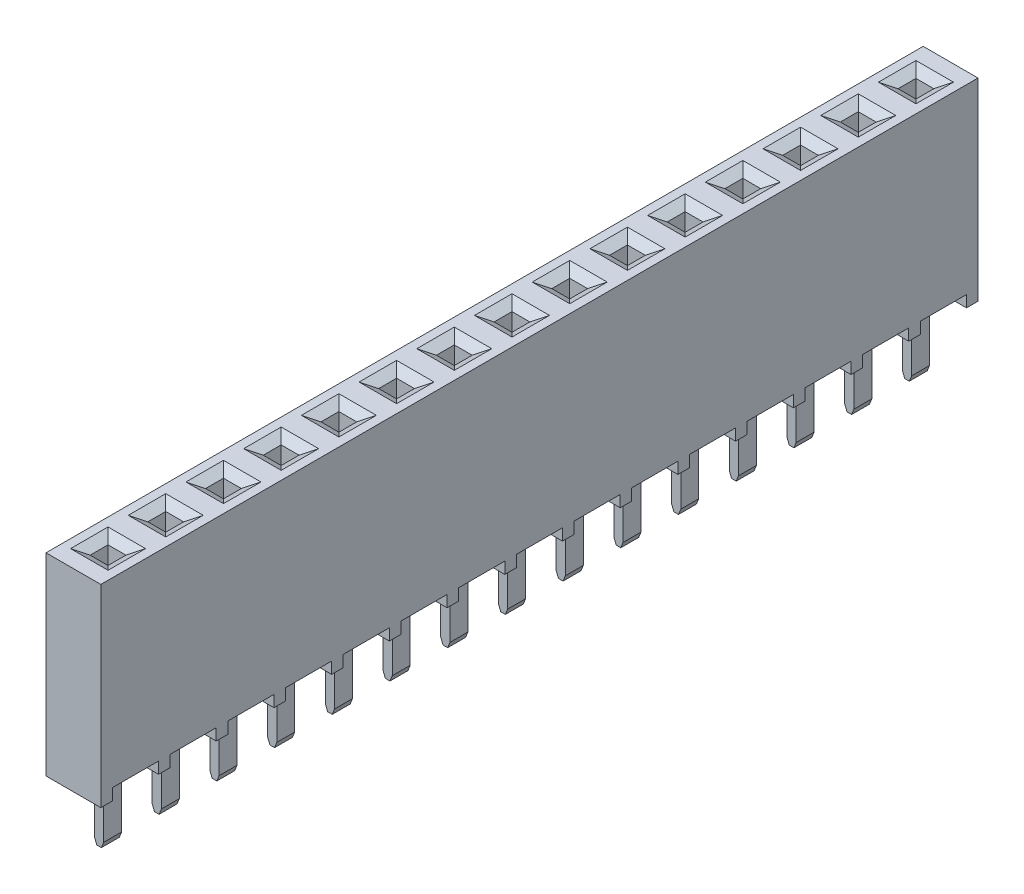
SolidWorks part; units mm, degrees
ref_plane "Front" through (0, 0, 0) normal (0, 0, 1) x (1, 0, 0)
ref_plane "Top" through (0, 0, 0) normal (0, 1, 0) x (1, 0, 0)
ref_plane "Right" through (0, 0, 0) normal (1, 0, 0) x (0, 0, -1)
sketch "Sketch1" plane through (0, 0, 0) normal (0, 1, 0) x (1, 0, 0)
  line L0 (-1.2065, -19.304) -> (1.2065, 19.304) construction
  line L1 (-1.2065, 19.304) -> (1.2065, 19.304)
  line L2 (-1.2065, 19.304) -> (-1.2065, -19.304)
  line L3 (-1.2065, -19.304) -> (1.2065, -19.304)
  line L4 (1.2065, 19.304) -> (1.2065, -19.304)
  dimension "D1" = 38.608
  dimension "D2" = 2.413
extrude "Main Body" add sketch "Sketch1" along normal blind 8.509
ref_plane "Plane1" through (0, 0, -15.24) normal (0, 0, -1) x (-1, 0, 0)
ref_plane "Plane2" through (0, 0, -17.78) normal (0, 0, -1) x (-1, 0, 0)
ref_plane "Plane3" through (0, 0, 0) normal (0, 0, 1) x (1, 0, 0)
ref_plane "Plane4" through (0, 0, -2.54) normal (0, 0, 1) x (1, 0, 0)
sketch "Sketch5" plane through (1.2065, 0, 0) normal (1, 0, 0) x (0, 0, -1)
  line L0 (-19.304, 0) -> (19.304, 0) construction
  line L1 (16.764, 0) -> (18.796, 0)
  line L2 (16.764, 0) -> (16.764, 0.508)
  line L3 (16.764, 0.508) -> (18.796, 0.508)
  line L4 (18.796, 0) -> (18.796, 0.508)
  line L5 (17.78, 0.7418) -> (17.78, -0.7099) construction
  line L6 (19.304, 8.509) -> (19.304, 0) construction
  dimension "D1" = 0.508
  dimension "D2" = 1.524
  dimension "D3" = 0.508
extrude "Cut-Extrude2" cut sketch "Sketch5" against normal up to next
pattern_linear "LPattern1" count 15 spacing 2.54 along (0, 0, 1) of "Cut-Extrude2"
sketch "Sketch2" plane through (0, 8.509, 0) normal (0, 1, 0) x (-1, 0, 0)
  line L0 (0, -0.6833) -> (0, -4.4888) construction
  line L1 (-0.3937, -18.1737) -> (0.3937, -18.1737)
  line L2 (-0.3937, -18.1737) -> (-0.3937, -17.3863)
  line L3 (-0.3937, -17.3863) -> (0.3937, -17.3863)
  line L4 (0.3937, -18.1737) -> (0.3937, -17.3863)
  line L5 (0, 0) -> (-2.54, 0) construction
  line L6 (0.3937, -18.1737) -> (-0.3937, -17.3863) construction
  line L8 (-1.2065, -19.304) -> (1.2065, -19.304) construction
  line L9 (-1.2065, 19.304) -> (-1.2065, -19.304) construction
  point P8 (0, -17.78)
  dimension "D1" = 1.524
  dimension "D2" = 0.7874
  dimension "D3" = 0.7874
  dimension "D4" = 1.2065
extrude "Cut-Extrude1" cut sketch "Sketch2" against normal through all
chamfer "Chamfer1" distance 0.4318 angle 30 4 edges at (0, 8.509, -18.1737) (-0.3937, 8.509, -17.78) (0, 8.509, -17.3863) (0.3937, 8.509, -17.78) first distance on face at (0, 8.509, -17.78)
pattern_linear "LPattern2" count 15 spacing 2.54 along (0, 0, 1) of "Chamfer1", "Cut-Extrude1"
sketch "Sketch4" plane through (0, 0, -17.78) normal (0, 0, -1) x (-1, 0, 0)
  line L0 (0, 2.0688) -> (0, -17.6627) construction
  line L1 (0.3937, 0.508) -> (0.3937, 8.2597) construction
  line L2 (-0.3937, 0.508) -> (-0.3937, 8.2597) construction
  line L3 (-0.3937, 1.016) -> (0.3937, 1.016)
  line L5 (-0.2032, 0.889) -> (-0.2032, -2.3876)
  line L6 (-0.1016, -2.6416) -> (0.1016, -2.6416)
  line L7 (0.2032, 0.889) -> (0.2032, -2.3876)
  line L8 (0.1016, -2.6416) -> (0.2032, -2.3876)
  line L9 (-0.2032, -2.3876) -> (-0.1016, -2.6416)
  line L10 (-1.2065, 0) -> (1.2065, 0) construction
  line L11 (0.3937, 1.016) -> (0.3937, 0.889)
  line L12 (0.3937, 0.889) -> (0.2032, 0.889)
  line L13 (-0.2032, 0.889) -> (-0.3937, 0.889)
  line L14 (-0.3937, 0.889) -> (-0.3937, 1.016)
  dimension "D1" = 0.254
  dimension "D2" = 0.2032
  dimension "D3" = 0.4064
  dimension "D4" = 2.6416
  dimension "D5" = 0.7874
  dimension "D6" = 0.889
  dimension "D7" = 1.016
extrude "PIN" add sketch "Sketch4" along normal mid plane 0.7874
pattern_linear "LPattern4" count 15 spacing 2.54 along (0, 0, 1) of "PIN"
sketch "Sketch7" plane through (0, 0, -17.78) normal (0, 0, -1) x (-1, 0, 0)
  line L0 (-0.2032, 1.016) -> (-0.2032, -0.9144)
  line L1 (0.6096, -1.3208) -> (1.4605, -1.3208)
  line L2 (1.4605, -1.3208) -> (1.4605, -1.7272)
  line L3 (1.4605, -1.7272) -> (0.6096, -1.7272)
  line L4 (0.2032, -0.9144) -> (0.2032, 1.016)
  line L5 (-0.2032, 1.016) -> (-0.3937, 1.016)
  line L6 (0, 1.4788) -> (0, -2.2478) construction
  line L10 (1.2065, 8.509) -> (1.2065, 0) construction
  line L11 (-0.3937, 1.016) -> (-0.3937, 1.27)
  line L12 (-0.3937, 1.27) -> (0.3937, 1.27)
  line L13 (0.3937, 1.27) -> (0.3937, 1.016)
  line L14 (0.3937, 1.016) -> (0.2032, 1.016)
  line L16 (1.4605, -1.524) -> (-2.3476, -1.524) construction
  line L17 (-1.2065, 0) -> (1.2065, 0) construction
  line L18 (1.2065, 0.508) -> (-1.2065, 0.508) construction
  arc A0 (-0.2032, -0.9144) -> (0.6096, -1.7272) centre (0.6096, -0.9144) ccw
  arc A1 (0.6096, -1.3208) -> (0.2032, -0.9144) centre (0.6096, -0.9144) cw
  dimension "D9" = 0.8128
  dimension "D10" = 0.4064
  dimension "D1" = 1.2065
  dimension "D2" = 0.4064
  dimension "D3" = 0.4064
  dimension "D4" = 1.524
  dimension "D6" = 0.7874
  dimension "D7" = 0.762
  dimension "D8" = 0.254
  dimension "A" = 0.254
sketch "Sketch8" plane through (0, 0, -15.24) normal (0, 0, -1) x (-1, 0, 0)
  line L0 (0.2032, 1.016) -> (0.2032, -0.9144)
  line L1 (-0.3937, 1.27) -> (0.3937, 1.27)
  line L2 (1.2065, 8.509) -> (1.2065, 0) construction
  line L3 (0.3937, 1.016) -> (0.2032, 1.016)
  line L5 (-0.3937, 1.016) -> (-0.3937, 1.27)
  line L6 (0.3937, 1.016) -> (0.3937, 1.27)
  line L7 (-1.2065, 0) -> (1.2065, 0) construction
  line L8 (-0.2032, 1.016) -> (-0.2032, -0.9144)
  line L9 (0, 1.9479) -> (0, -2.4889) construction
  line L10 (2.9301, -1.524) -> (0.4606, -1.524) construction
  line L11 (1.2065, 8.509) -> (1.2065, 0) construction
  line L13 (-0.2032, 1.016) -> (-0.2032, -3.4544)
  line L15 (0.6096, -1.7272) -> (1.4605, -1.7272)
  line L16 (1.4605, -1.7272) -> (1.4605, -1.3208)
  line L17 (1.4605, -1.3208) -> (0.6096, -1.3208)
  line L18 (0.6096, -4.2672) -> (1.4605, -4.2672)
  line L19 (0.2032, -3.4544) -> (0.2032, 1.016)
  line L20 (1.4605, -3.8608) -> (0.6096, -3.8608)
  line L21 (1.4605, -4.2672) -> (1.4605, -3.8608)
  line L22 (0.3937, 1.27) -> (-0.3937, 1.27)
  line L23 (-0.3937, 1.016) -> (-0.2032, 1.016)
  line L24 (0.2032, 1.016) -> (0.3937, 1.016)
  line L25 (0.3937, 1.016) -> (0.3937, 1.27)
  line L26 (-0.3937, 1.016) -> (-0.3937, 1.27)
  line L27 (0.3937, 0.508) -> (0.3937, 0.889) construction
  line L28 (-0.3937, 0.508) -> (-0.3937, 0.889) construction
  line L29 (0, 1.27) -> (0, -2.4889) construction
  line L30 (1.4605, -4.064) -> (1.27, -4.064) construction
  line L31 (-0.2032, 1.016) -> (-0.3937, 1.016)
  arc A0 (0.6096, -3.8608) -> (0.2032, -3.4544) centre (0.6096, -3.4544) cw
  arc A1 (0.6096, -4.2672) -> (-0.2032, -3.4544) centre (0.6096, -3.4544) cw
  arc A2 (0.6096, -1.7272) -> (-0.2032, -0.9144) centre (0.6096, -0.9144) cw
  arc A3 (0.6096, -1.3208) -> (0.2032, -0.9144) centre (0.6096, -0.9144) cw
  dimension "D5" = 0.8128
  dimension "D6" = 0.4064
  dimension "D14" = 0.4064
  dimension "D15" = 0.8128
  dimension "D1" = 1.27
  dimension "D2" = 0.254
  dimension "D3" = 0.4064
  dimension "D4" = 0.4064
  dimension "D7" = 1.524
  dimension "D8" = 0.4064
  dimension "D9" = 0.254
  dimension "D10" = 2.54
  dimension "D11" = 0.4064
  dimension "D12" = 1.2065
sketch "Sketch9" plane through (0, 0, -15.24) normal (0, 0, -1) x (-1, 0, 0)
  line L0 (0, 1.6049) -> (0, -3.2713) construction
  line L1 (-2.9337, 1.016) -> (-2.9337, 1.27)
  line L2 (0.3937, 1.27) -> (-0.3937, 1.27)
  line L4 (-2.1463, 1.27) -> (-2.9337, 1.27)
  line L5 (0.3937, 1.016) -> (0.3937, 1.27)
  line L6 (-2.3368, 1.016) -> (-2.1463, 1.016)
  line L7 (-0.3937, 1.016) -> (-0.3937, 1.27)
  line L8 (-0.3937, 1.016) -> (-0.2032, 1.016)
  line L10 (0.3937, 1.27) -> (-0.3937, 1.27)
  line L11 (-2.1463, 1.27) -> (-2.1463, 1.016)
  line L12 (-1.9304, -4.2672) -> (1.4605, -4.2672)
  line L13 (1.4605, -4.2672) -> (1.4605, -3.8608)
  line L14 (1.4605, -3.8608) -> (-1.9304, -3.8608)
  line L15 (0.2032, -5.9944) -> (0.2032, 1.016)
  line L16 (-0.3937, 1.016) -> (-0.3937, 1.27)
  line L17 (-0.2032, 1.016) -> (-0.2032, -5.9944)
  line L18 (-0.3937, 1.016) -> (-0.2032, 1.016)
  line L19 (0.2032, 1.016) -> (0.3937, 1.016)
  line L20 (0.3937, 1.27) -> (0.3937, 1.016)
  line L21 (0.2032, -0.9144) -> (0.2032, 1.016)
  line L22 (-0.2032, 1.016) -> (-0.2032, -0.9144)
  line L24 (1.2065, 8.509) -> (1.2065, 0) construction
  line L25 (1.4605, -1.7272) -> (1.4605, -1.3208)
  line L26 (1.4605, -1.3208) -> (0.6096, -1.3208)
  line L27 (-2.3368, -3.4544) -> (-2.3368, 1.016)
  line L29 (-2.7432, 1.016) -> (-2.7432, -3.4544)
  line L31 (-1.2065, 0) -> (1.2065, 0) construction
  line L32 (0.6096, -1.7272) -> (1.4605, -1.7272)
  line L34 (6.2865, -1.524) -> (4.283, -1.524) construction
  line L35 (6.2865, -4.064) -> (4.7316, -4.064) construction
  line L40 (-2.7432, 1.016) -> (-2.9337, 1.016)
  line L41 (-2.54, 1.27) -> (-2.54, -1.7272) construction
  line L42 (0.2032, 1.016) -> (0.3937, 1.016)
  line L43 (0.3937, 0.508) -> (0.3937, 0.889) construction
  line L44 (-0.3937, 0.508) -> (-0.3937, 0.889) construction
  line L45 (0, 1.27) -> (0, -1.198) construction
  line L46 (0.6096, -6.4008) -> (1.4605, -6.4008)
  line L47 (1.4605, -6.4008) -> (1.4605, -6.8072)
  line L48 (1.4605, -6.8072) -> (0.6096, -6.8072)
  line L49 (6.1112, -6.604) -> (4.5563, -6.604) construction
  arc A0 (0.2032, -0.9144) -> (0.6096, -1.3208) centre (0.6096, -0.9144) ccw
  arc A1 (-0.2032, -0.9144) -> (0.6096, -1.7272) centre (0.6096, -0.9144) ccw
  arc A2 (-1.9304, -4.2672) -> (-2.7432, -3.4544) centre (-1.9304, -3.4544) cw
  arc A3 (-1.9304, -3.8608) -> (-2.3368, -3.4544) centre (-1.9304, -3.4544) cw
  arc A4 (0.6096, -6.4008) -> (0.2032, -5.9944) centre (0.6096, -5.9944) cw
  arc A5 (0.6096, -6.8072) -> (-0.2032, -5.9944) centre (0.6096, -5.9944) cw
  dimension "D7" = 1.27
  dimension "D8" = 0.254
  dimension "D11" = 0.4064
  dimension "D12" = 0.8128
  dimension "D4" = 0.4064
  dimension "D5" = 0.8128
  dimension "D15" = 0.4064
  dimension "D16" = 0.8128
  dimension "D2" = 1.524
  dimension "D3" = 0.4064
  dimension "D6" = 0.4064
  dimension "D9" = 1.2065
  dimension "D10" = 2.54
  dimension "D13" = 0.4064
  dimension "D14" = 5.08
  dimension "D17" = 0.4064
  dimension "D18" = 2.54
  dimension "D19" = 0.7874
  dimension "D20" = 0.7874
  dimension "A" = 0.254
sketch "Sketch10" plane through (0, 0, -15.24) normal (0, 0, -1) x (-1, 0, 0)
  line L0 (-2.54, -14.478) -> (-2.54, 0.635)
  line L2 (-0.508, -16.51) -> (-0.2286, -16.51)
  line L3 (-1.2065, 0) -> (1.2065, 0) construction
  line L4 (1.2065, 8.509) -> (1.2065, 0) construction
  arc A0 (-2.54, -14.478) -> (-0.508, -16.51) centre (-0.508, -14.478) ccw
  dimension "D1" = 2.032
  dimension "D5" = 0.635
  dimension "D2" = 16.51
  dimension "D3" = 0.2794
  dimension "D4" = 3.7465
sketch "Sketch6" plane through (0, 0.508, 0) normal (0, 1, 0) x (-1, 0, 0)
  line L0 (-1.2065, -19.304) -> (1.2065, -19.304) construction
  line L3 (-1.7145, -18.6055) -> (-3.3655, -18.6055)
  line L6 (-3.3655, -18.6055) -> (-3.3655, -16.9545)
  line L8 (-3.3655, -16.9545) -> (-1.7145, -16.9545)
  line L10 (-1.7145, -16.9545) -> (-1.7145, -18.6055)
  line L11 (-3.3655, -17.78) -> (-1.7145, -17.78) construction
  line L12 (-2.54, -18.6055) -> (-2.54, -16.9545) construction
  line L14 (1.2065, -19.304) -> (1.2065, 19.304) construction
  dimension "D1" = 1.651
  dimension "D2" = 3.7465
  dimension "D3" = 1.524
sketch "Sketch11" plane through (0, 0, -15.24) normal (0, 0, -1) x (-1, 0, 0)
  line L0 (-0.2032, 1.016) -> (-0.2032, -0.4572)
  line L1 (-2.5781, -1.27) -> (-0.6096, -1.27)
  line L2 (-0.6096, -0.8636) -> (-2.5781, -0.8636)
  line L3 (-2.5781, -0.8636) -> (-2.5781, -1.27)
  line L4 (0.2032, -0.4572) -> (0.2032, 1.016)
  line L5 (0.3937, 1.27) -> (0.3937, 1.016)
  line L6 (0.3937, 1.016) -> (0.2032, 1.016)
  line L7 (0.3937, 1.27) -> (-0.3937, 1.27)
  line L8 (-0.3937, 1.27) -> (-0.3937, 1.016)
  line L9 (-0.3937, 1.016) -> (-0.2032, 1.016)
  line L10 (-0.3937, 0.508) -> (-0.3937, 0.889) construction
  line L11 (-1.2065, 8.509) -> (-1.2065, 0) construction
  line L12 (0, 1.27) -> (0, -1.1346) construction
  line L13 (-1.2065, 0) -> (1.2065, 0) construction
  arc A0 (-0.2032, -0.4572) -> (-0.6096, -0.8636) centre (-0.6096, -0.4572) cw
  arc A1 (-0.6096, -1.27) -> (0.2032, -0.4572) centre (-0.6096, -0.4572) ccw
  dimension "D7" = 1.27
  dimension "D4" = 0.4064
  dimension "D5" = 0.8128
  dimension "D1" = 0.4064
  dimension "D2" = 1.2065
  dimension "D3" = 1.27
  dimension "D6" = 0.4064
  dimension "L" = 2.5781
sketch "Sketch12" plane through (0, 0, -17.78) normal (0, 0, -1) x (-1, 0, 0)
  line L1 (0.3937, 1.27) -> (-0.3937, 1.27)
  line L3 (-0.3937, 1.016) -> (-0.2032, 1.016)
  line L5 (0.3937, 1.016) -> (0.3937, 1.27)
  line L6 (0, 1.27) -> (0, -2.7927) construction
  line L7 (2.5781, -0.8636) -> (2.5781, -1.27)
  line L8 (2.5781, -1.27) -> (0.6096, -1.27)
  line L9 (0.6096, -0.8636) -> (2.5781, -0.8636)
  line L10 (0.2032, 1.016) -> (0.3937, 1.016)
  line L11 (1.2065, 8.509) -> (1.2065, 0) construction
  line L12 (0.2032, -0.4572) -> (0.2032, 1.016)
  line L13 (-1.2065, 0) -> (1.2065, 0) construction
  line L14 (-0.2032, 1.016) -> (-0.2032, -0.4572)
  line L19 (-0.3937, 1.016) -> (-0.3937, 1.27)
  arc A0 (0.6096, -0.8636) -> (0.2032, -0.4572) centre (0.6096, -0.4572) cw
  arc A1 (0.6096, -1.27) -> (-0.2032, -0.4572) centre (0.6096, -0.4572) cw
  dimension "D7" = 1.27
  dimension "D11" = 0.8128
  dimension "D3" = 1.2065
  dimension "D4" = 0.7874
  dimension "D5" = 1.27
  dimension "D6" = 0.254
  dimension "D8" = 0.4064
  dimension "D10" = 0.4064
  dimension "L" = 2.5781
sketch "Sketch19" plane through (0, 0, 0) normal (0, 0, 1) x (1, 0, 0)
  line L0 (-3.1115, -1.7272) -> (-2.8964, -1.7272)
  line L1 (-1.5486, -1.7272) -> (-1.3335, -1.7272)
  line L2 (-1.3335, -1.7272) -> (-1.3335, -1.3208)
  line L3 (-1.3335, -1.3208) -> (-3.1115, -1.3208)
  line L4 (-3.1115, -1.3208) -> (-3.1115, -1.7272)
  line L6 (-3.1115, -1.9304) -> (-0.9396, -1.9304) construction
  line L7 (-3.1115, -1.524) -> (-1.3335, -1.524) construction
  line L8 (8.4718, 0) -> (-8.4718, 0) construction
  line L9 (-1.2065, 8.509) -> (-1.2065, 0) construction
  line L10 (-2.2225, -1.1176) -> (-2.2225, -1.524) construction
  arc A0 (-2.6718, -1.7949) -> (-2.8964, -1.7272) centre (-2.8964, -2.1336) ccw
  arc A1 (-2.6718, -1.7949) -> (-1.7732, -1.7949) centre (-2.2225, -1.1176) ccw
  arc A2 (-1.5486, -1.7272) -> (-1.7732, -1.7949) centre (-1.5486, -2.1336) ccw
  dimension "D1" = 0.8128
  dimension "D6" = 0.4064
  dimension "D2" = 1.524
  dimension "D3" = 0.4064
  dimension "D4" = 0.2032
  dimension "D5" = 1.016
  dimension "D7" = 1.778
sketch "Sketch20" plane through (0, 0, 0) normal (0, 0, 1) x (1, 0, 0)
  line L0 (-2.5334, -1.524) -> (-1.2951, -1.524) construction
  line L1 (-1.2065, 8.509) -> (-1.2065, 0) construction
  line L4 (-2.8964, -1.3208) -> (-3.1115, -1.3208)
  line L5 (-3.1115, -1.3208) -> (-3.1115, -1.0668)
  line L6 (-3.1115, -1.0668) -> (-1.3335, -1.0668)
  line L7 (-1.5486, -1.3208) -> (-1.3335, -1.3208)
  line L8 (-1.3335, -1.3208) -> (-1.3335, -1.0668)
  line L9 (-2.2225, -1.524) -> (-2.2225, -0.6068) construction
  line L10 (-1.2065, 0) -> (1.2065, 0) construction
  arc A0 (-2.6718, -1.3885) -> (-1.7732, -1.3885) centre (-2.2225, -0.7112) ccw
  arc A1 (-2.6718, -1.3885) -> (-2.8964, -1.3208) centre (-2.8964, -1.7272) ccw
  arc A2 (-1.7732, -1.3885) -> (-1.5486, -1.3208) centre (-1.5486, -1.7272) cw
  dimension "D1" = 1.6256
  dimension "D4" = 0.4064
  dimension "D2" = 1.016
  dimension "D3" = 1.524
  dimension "D5" = 0.254
  dimension "D6" = 0.4064
  dimension "D7" = 1.778
sketch "Sketch45" plane through (0, 0, -2.54) normal (0, 0, 1) x (1, 0, 0)
  line L0 (-3.1115, -1.3208) -> (-3.048, -1.3208)
  line L1 (-1.3335, -1.3208) -> (-3.1115, -1.3208) construction
  line L2 (-2.931, -1.3036) -> (-2.398, -1.1434)
  line L3 (-2.047, -1.1434) -> (-1.514, -1.3036)
  line L4 (-1.397, -1.3208) -> (-1.3335, -1.3208)
  line L5 (-1.3335, -1.3208) -> (-1.3335, -1.7272)
  line L6 (-1.3335, -1.7272) -> (-3.1115, -1.7272)
  line L7 (-3.1115, -1.7272) -> (-3.1115, -1.3208)
  arc A0 (-3.048, -1.3208) -> (-2.931, -1.3036) centre (-3.048, -0.9144) ccw
  arc A1 (-2.398, -1.1434) -> (-2.047, -1.1434) centre (-2.2225, -1.7272) cw
  arc A2 (-1.514, -1.3036) -> (-1.397, -1.3208) centre (-1.397, -0.9144) ccw
  dimension "D1" = 0.2032
  dimension "D2" = 0.0635
  dimension "D3" = 0.4064
  dimension "D4" = 0.6096
sketch "Sketch46" plane through (0, 0, -2.54) normal (0, 0, 1) x (1, 0, 0)
  line L1 (-1.5486, -1.3208) -> (-1.3335, -1.3208) construction
  line L3 (-3.1115, -1.3208) -> (-3.1115, -1.0668) construction
  line L4 (-3.1115, -1.0668) -> (-1.3335, -1.0668) construction
  line L5 (-1.3335, -1.3208) -> (-1.3335, -1.0668) construction
  line L6 (-2.8964, -1.3208) -> (-3.1115, -1.3208) construction
  line L10 (-1.2951, -1.524) -> (-3.1115, -1.524) construction
  line L11 (-3.1115, -1.9812) -> (-1.3335, -1.9812)
  line L12 (-3.1115, -1.7272) -> (-3.1115, -1.9812)
  line L13 (-2.8964, -1.7272) -> (-3.1115, -1.7272)
  line L14 (-1.5486, -1.7272) -> (-1.3335, -1.7272)
  line L15 (-1.3335, -1.7272) -> (-1.3335, -1.9812)
  arc A0 (-2.6718, -1.3885) -> (-1.7732, -1.3885) centre (-2.2225, -0.7112) ccw construction
  arc A3 (-2.6718, -1.3885) -> (-2.8964, -1.3208) centre (-2.8964, -1.7272) ccw construction
  arc A6 (-2.6718, -1.6595) -> (-2.8964, -1.7272) centre (-2.8964, -1.3208) cw
  arc A7 (-1.5486, -1.7272) -> (-1.7732, -1.6595) centre (-1.5486, -1.3208) cw
  arc A8 (-2.6718, -1.6595) -> (-1.7732, -1.6595) centre (-2.2225, -2.3368) cw
sketch "Sketch27" plane through (0, 0, 0) normal (0, 0, 1) x (1, 0, 0)
  line L0 (-3.8171, -6.1976) -> (-2.3191, -6.1976) construction
  line L3 (-2.2225, -7.0104) -> (-2.2225, -2.6186) construction
  line L4 (-1.2065, 8.509) -> (-1.2065, 0) construction
  line L5 (-2.8964, -6.4008) -> (-3.1115, -6.4008)
  line L6 (-3.1115, -6.4008) -> (-3.1115, -6.8072)
  line L7 (-3.1115, -6.8072) -> (-1.3335, -6.8072)
  line L8 (-1.3335, -6.8072) -> (-1.3335, -6.4008)
  line L9 (-1.3335, -6.4008) -> (-1.5486, -6.4008)
  line L10 (-3.1115, -6.604) -> (-1.3335, -6.604) construction
  line L11 (-1.2065, 0) -> (1.2065, 0) construction
  arc A0 (-1.7732, -6.3331) -> (-2.6718, -6.3331) centre (-2.2225, -7.0104) ccw
  arc A1 (-1.5486, -6.4008) -> (-1.7732, -6.3331) centre (-1.5486, -5.9944) cw
  arc A2 (-2.8964, -6.4008) -> (-2.6718, -6.3331) centre (-2.8964, -5.9944) ccw
  dimension "D1" = 1.6256
  dimension "D7" = 0.4064
  dimension "D2" = 0.4064
  dimension "D3" = 1.016
  dimension "D5" = 0.4064
  dimension "D6" = 1.778
  dimension "D" = 6.604
sketch "Sketch28" plane through (0, 0, 0) normal (0, 0, 1) x (1, 0, 0)
  line L0 (-4.004, -6.604) -> (-2.6238, -6.604) construction
  line L3 (-2.2225, -7.4168) -> (-2.2225, -2.6456) construction
  line L4 (-1.2065, 8.509) -> (-1.2065, 0) construction
  line L5 (-1.2065, 0) -> (1.2065, 0) construction
  line L6 (-2.8964, -6.8072) -> (-3.1115, -6.8072)
  line L7 (-3.1115, -6.8072) -> (-3.1115, -7.0612)
  line L8 (-3.1115, -7.0612) -> (-1.3335, -7.0612)
  line L9 (-1.3335, -7.0612) -> (-1.3335, -6.8072)
  line L10 (-1.3335, -6.8072) -> (-1.5486, -6.8072)
  arc A0 (-1.7732, -6.7395) -> (-2.6718, -6.7395) centre (-2.2225, -7.4168) ccw
  arc A1 (-1.5486, -6.8072) -> (-1.7732, -6.7395) centre (-1.5486, -6.4008) cw
  arc A2 (-2.8964, -6.8072) -> (-2.6718, -6.7395) centre (-2.8964, -6.4008) ccw
  dimension "D1" = 1.6256
  dimension "D7" = 0.4064
  dimension "D3" = 1.016
  dimension "D4" = 0.2032
  dimension "D5" = 0.254
  dimension "D6" = 1.778
  dimension "D" = 6.604
sketch "Sketch38" plane through (0, 0, -2.54) normal (0, 0, 1) x (1, 0, 0)
  line L0 (-1.016, -1.016) -> (2.1645, -1.016) construction
  line L1 (0, -1.905) -> (0, -0.127) construction
  line L2 (0.4064, -0.4657) -> (0.4064, -2.0349) construction
  line L5 (0.2032, -0.1782) -> (0.2032, -0.127)
  line L6 (0.2032, -0.127) -> (-0.2032, -0.127)
  line L7 (-0.2032, -0.127) -> (-0.2032, -1.905)
  line L8 (-1.2065, 0) -> (1.2065, 0) construction
  line L9 (-0.2032, -1.905) -> (0.2032, -1.905)
  line L10 (0.2032, -1.905) -> (0.2032, -1.8538)
  line L12 (-1.2065, 8.509) -> (-1.2065, 0) construction
  arc A0 (0.2032, -0.1782) -> (0.2484, -0.3644) centre (0.6096, -0.1782) ccw
  arc A1 (0.2484, -1.6676) -> (0.2484, -0.3644) centre (-1.016, -1.016) ccw
  arc A2 (0.2032, -1.8538) -> (0.2484, -1.6676) centre (0.6096, -1.8538) cw
  dimension "D1" = 1.4224
  dimension "D5" = 0.4064
  dimension "D4" = 1.778
  dimension "D6" = 0.4064
  dimension "D2" = 1.2065
  dimension "D3" = 1.016
  dimension "D7" = 0.4064
sketch "Sketch39" plane through (0, 0, -2.54) normal (0, 0, 1) x (1, 0, 0)
  line L0 (-1.4224, -1.016) -> (1.423, -1.016) construction
  line L1 (0, -1.016) -> (0, -2.3641) construction
  line L2 (-1.2065, 8.509) -> (-1.2065, 0) construction
  line L3 (-1.2065, 0) -> (1.2065, 0) construction
  line L4 (-0.2032, -0.2834) -> (-0.2032, -0.127)
  line L5 (-0.2032, -0.127) -> (-0.4572, -0.127)
  line L6 (-0.4572, -0.127) -> (-0.4572, -1.905)
  line L7 (-0.4572, -1.905) -> (-0.2032, -1.905)
  line L8 (-0.2032, -1.905) -> (-0.2032, -1.7486)
  arc A0 (-0.2032, -1.7486) -> (-0.2032, -0.2834) centre (-1.4224, -1.016) ccw
  dimension "D1" = 2.8448
  dimension "D2" = 1.016
  dimension "D3" = 0.1564
  dimension "D4" = 0.254
  dimension "D5" = 1.778
  dimension "D6" = 1.2065
sketch "Sketch40" plane through (0, 8.509, 0) normal (0, 1, 0) x (-1, 0, 0)
  circle A0 centre (0, 0) radius 1.7526
  dimension "D1" = 3.5052
sketch "Sketch41" plane through (0, 0, 0) normal (0, 0, 1) x (1, 0, 0)
  line L0 (0, 0) -> (0, 12.0579) construction
  line L1 (-2.8283, 4.7606) -> (-2.8141, 4.7868)
  line L2 (-2.6496, 5.6392) -> (-2.9701, 8.4292)
  line L3 (-2.7178, 8.7122) -> (2.7178, 8.7122)
  line L4 (-2.9718, 10.4747) -> (-2.9718, 5.0805) construction
  line L7 (-2.7178, 8.509) -> (2.7178, 8.509)
  line L8 (-2.4477, 5.6624) -> (-2.7683, 8.4524)
  line L9 (2.8283, 4.7606) -> (2.6354, 4.6902)
  line L10 (-2.8283, 4.7606) -> (-2.6354, 4.6902)
  line L11 (2.4477, 5.6624) -> (2.7683, 8.4524)
  line L12 (2.6496, 5.6392) -> (2.9701, 8.4292)
  line L13 (2.8283, 4.7606) -> (2.8141, 4.7868)
  line L14 (-1.2065, 0) -> (1.2065, 0) construction
  arc A0 (-2.9701, 8.4292) -> (-2.7178, 8.7122) centre (-2.7178, 8.4582) cw
  arc A1 (-2.8141, 4.7868) -> (-2.6496, 5.6392) centre (-4.0849, 5.4742) ccw
  arc A2 (-2.7683, 8.4524) -> (-2.7178, 8.509) centre (-2.7178, 8.4582) cw
  arc A3 (-2.6354, 4.6902) -> (-2.4477, 5.6624) centre (-4.0849, 5.4742) ccw
  arc A4 (2.6354, 4.6902) -> (2.4477, 5.6624) centre (4.0849, 5.4742) cw
  arc A5 (2.7683, 8.4524) -> (2.7178, 8.509) centre (2.7178, 8.4582) ccw
  arc A6 (2.8141, 4.7868) -> (2.6496, 5.6392) centre (4.0849, 5.4742) cw
  arc A7 (2.9701, 8.4292) -> (2.7178, 8.7122) centre (2.7178, 8.4582) ccw
  point P6 (0, 8.7122)
  point P31 (0, 8.509)
  dimension "D1" = 0.254
  dimension "D4" = 0.2032
  dimension "D6" = 1.4448
  dimension "D2" = 8.7122
  dimension "D3" = 2.9718
  dimension "D5" = 3.9516
  dimension "D7" = 2.79
  dimension "D8" = 0.3206
  dimension "D9" = 4.022
sketch "Sketch43" plane through (0, 8.509, 0) normal (0, 1, 0) x (-1, 0, 0)
  line L0 (2.4765, 0) -> (-2.4765, 0) construction
  line L1 (2.4765, -5.0165) -> (-2.4765, -5.0165)
  line L2 (2.4765, -5.0165) -> (2.4765, 5.0165)
  line L3 (2.4765, 5.0165) -> (-2.4765, 5.0165)
  line L4 (-2.4765, -5.0165) -> (-2.4765, 5.0165)
  dimension "D1" = 10.033
  dimension "D2" = 4.953
sketch "Polarize sketch" plane through (0, 8.509, 0) normal (0, 1, 0) x (-1, 0, 0)
  line L0 (-0.8915, -20.1905) -> (0.8865, -18.4125) construction
  line L1 (-0.8915, -20.1905) -> (0.8865, -20.1905)
  line L2 (-0.8915, -20.1905) -> (-0.8915, -18.4125)
  line L3 (-0.8915, -18.4125) -> (0.8865, -18.4125)
  line L4 (0.8865, -20.1905) -> (0.8865, -18.4125)
  line L5 (0.8865, -20.1905) -> (-0.0025, -19.3015) construction
  line L6 (0, -7.5404) -> (0, -10.8194) construction
  line L7 (-1.2065, -19.304) -> (1.2065, -19.304) construction
  line L11 (1.2065, -19.304) -> (1.2065, 19.304) construction
  dimension "D1" = 1.2065
  dimension "D2" = 1.778
  dimension "Width" = 0.0025
  dimension "Height" = 0.0025
sketch "Sketch44" plane through (0, 0, -19.304) normal (0, 0, -1) x (-1, 0, 0)
  line L0 (-1.2065, 5.4864) -> (-0.8255, 4.9784)
  line L1 (-1.2065, 8.509) -> (-1.2065, 0) construction
  line L2 (-0.8255, 4.2164) -> (-1.2065, 3.7084)
  line L3 (-1.2065, 3.7084) -> (-1.2065, 5.4864)
  line L4 (-1.3335, 4.5974) -> (-1.2065, 4.5974) construction
  line L5 (-1.2065, 8.509) -> (1.2065, 8.509) construction
  arc A0 (-0.8255, 4.9784) -> (-0.8255, 4.2164) centre (-1.3335, 4.5974) cw
  dimension "D3" = 0.508
  dimension "D4" = 0.635
  dimension "D1" = 1.778
  dimension "D2" = 3.9116
